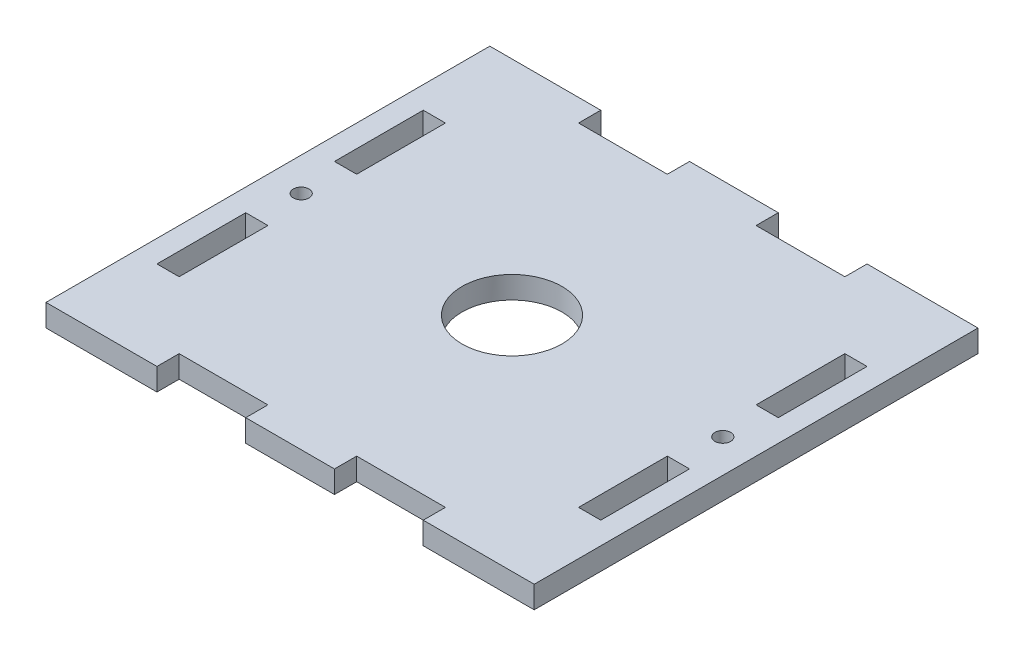
SolidWorks part; units mm, degrees
ref_plane "Front Plane" through (0, 0, 0) normal (0, 0, 1) x (1, 0, 0)
ref_plane "Top Plane" through (0, 0, 0) normal (0, 1, 0) x (1, 0, 0)
ref_plane "Right Plane" through (0, 0, 0) normal (1, 0, 0) x (0, 0, -1)
sketch "Sketch1" plane through (0, 0, 0) normal (0, 1, 0) x (1, 0, 0)
  line L1 (0, 0) -> (139.7, 0)
  line L2 (0, 0) -> (0, 127)
  line L3 (0, 127) -> (139.7, 127)
  line L4 (139.7, 0) -> (139.7, 127)
  dimension "D1" = 127
  dimension "D2" = 139.7
extrude "Boss-Extrude1" add sketch "Sketch1" along normal blind 6.35
sketch "Sketch13" plane through (0, 6.35, 0) normal (0, 1, 0) x (1, 0, 0)
  line L0 (0, 0) -> (139.7, 0) construction
  line L1 (31.75, 0) -> (57.15, 0)
  line L2 (31.75, 0) -> (31.75, 6.35)
  line L3 (31.75, 6.35) -> (57.15, 6.35)
  line L4 (57.15, 0) -> (57.15, 6.35)
  line L5 (82.55, 6.35) -> (107.95, 6.35)
  line L6 (107.95, 0) -> (107.95, 6.35)
  line L7 (82.55, 0) -> (107.95, 0)
  line L8 (82.55, 0) -> (82.55, 6.35)
  line L17 (31.75, 6.35) -> (82.55, 6.35) construction
  line L18 (0, 127) -> (0, 0) construction
  dimension "D1" = 25.4
  dimension "D2" = 6.35
  dimension "D4" = 50.8
  dimension "D5" = 31.75
  dimension "D3" = 2
extrude "Cut-Extrude6" cut sketch "Sketch13" against normal blind 6.35
pattern_linear "LPattern7" count 2 spacing 120.65 along (0, 0, -1) of "Cut-Extrude6"
sketch "Sketch14" plane through (0, 6.35, 0) normal (0, 1, 0) x (1, 0, 0)
  line L0 (0, 127) -> (0, 0) construction
  line L1 (6.35, 25.4) -> (12.7, 25.4)
  line L2 (6.35, 25.4) -> (6.35, 50.8)
  line L3 (6.35, 50.8) -> (12.7, 50.8)
  line L4 (12.7, 25.4) -> (12.7, 50.8)
  line L5 (0, 0) -> (31.75, 0) construction
  line L6 (127, 50.8) -> (133.35, 50.8)
  line L7 (127, 25.4) -> (127, 50.8)
  line L8 (133.35, 25.4) -> (133.35, 50.8)
  line L9 (127, 25.4) -> (133.35, 25.4)
  line L10 (127, 101.6) -> (133.35, 101.6)
  line L11 (127, 76.2) -> (127, 101.6)
  line L12 (133.35, 76.2) -> (133.35, 101.6)
  line L13 (127, 76.2) -> (133.35, 76.2)
  line L14 (6.35, 101.6) -> (12.7, 101.6)
  line L15 (6.35, 76.2) -> (6.35, 101.6)
  line L16 (12.7, 76.2) -> (12.7, 101.6)
  line L17 (6.35, 76.2) -> (12.7, 76.2)
  dimension "D1" = 25.4
  dimension "D2" = 6.35
  dimension "D3" = 6.35
  dimension "D4" = 25.4
  dimension "D5" = 2
  dimension "D6" = 2
extrude "Cut-Extrude7" cut sketch "Sketch14" against normal blind 6.35
hole_wizard "#8 Clearance Hole1" positions "Sketch16" profile "Sketch15" hole size "#8" standard "ANSI Inch"
sketch "Sketch16" plane through (0, 6.35, 0) normal (0, 1, 0) x (1, 0, 0)
  line L0 (12.7, 50.8) -> (6.35, 50.8) construction
  line L1 (6.35, 50.8) -> (6.35, 25.4) construction
  line L2 (133.35, 50.8) -> (127, 50.8) construction
  line L3 (127, 50.8) -> (127, 25.4) construction
  point P0 (9.525, 63.5)
  point P3 (9.525, 50.8)
  point P8 (130.175, 63.5)
  dimension "D1" = 12.7
  dimension "D2" = 3.175
  dimension "D3" = 12.7
  dimension "D4" = 3.175
sketch "Sketch15" plane through (9.525, 6.35, -63.5) normal (1, 0, 0) x (0, 0, 1)
  line L0 (0, 0) -> (0, 11.5107)
  line L1 (0, 11.5107) -> (2.2479, 10.16)
  line L2 (2.2479, 10.16) -> (2.2479, 0)
  line L5 (2.2479, 0) -> (0, 0)
  line L10 (0, 11.5107) -> (-2.2479, 10.16) construction
  line L11 (0, -6.35) -> (0, 107.95) construction
  dimension "Hole Dia." = 4.4958
  dimension "Hole Depth" = 10.16
  dimension "Drill Angle" = 118
sketch "Sketch18" plane through (0, 6.35, 0) normal (0, 1, 0) x (1, 0, 0)
  line L0 (0, 127) -> (0, 0) construction
  circle A0 centre (69.85, 63.5) radius 14.2875
  point P4 (0, 63.5)
  dimension "D1" = 28.575
  dimension "D2" = 69.85
extrude "Cut-Extrude9" cut sketch "Sketch18" against normal blind 7.62
equation "\"THICK\"= .25"
